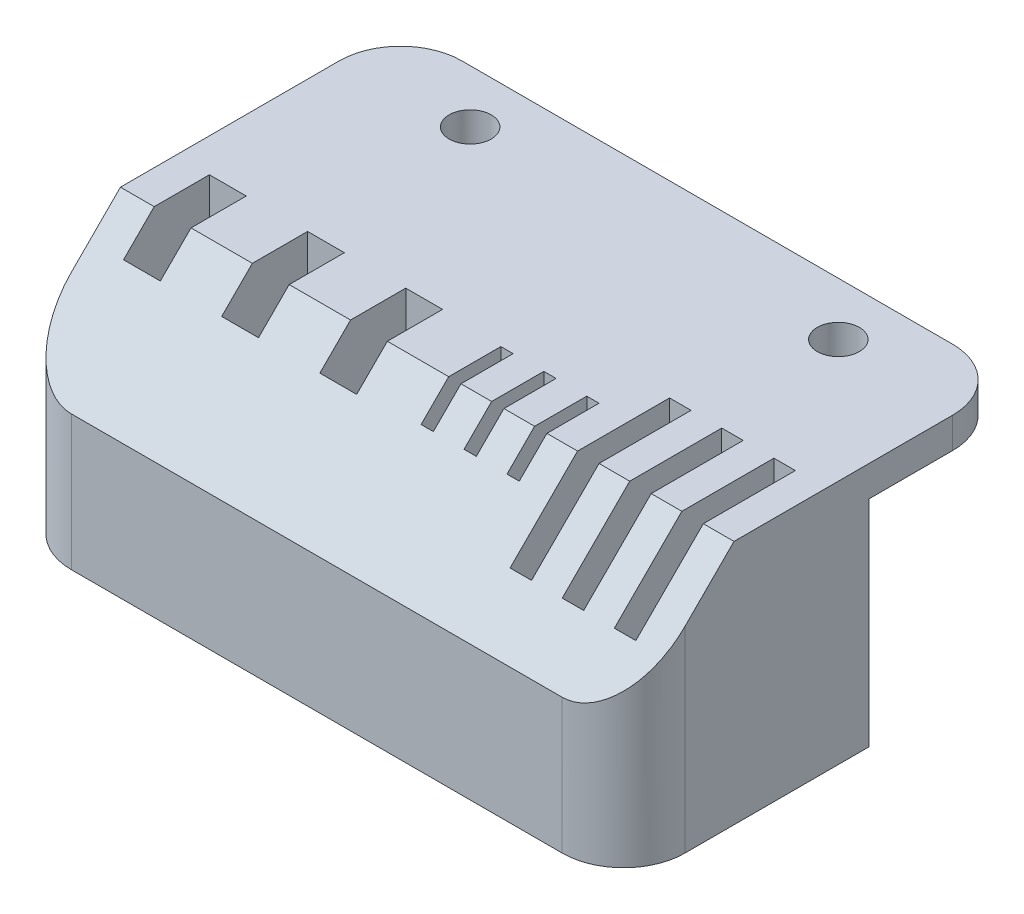
SolidWorks part; units mm, degrees
ref_plane "Front" through (0, 0, 0) normal (0, 0, 1) x (1, 0, 0)
ref_plane "Top" through (0, 0, 0) normal (0, 1, 0) x (1, 0, 0)
ref_plane "Right" through (0, 0, 0) normal (1, 0, 0) x (0, 0, -1)
sketch "Sketch1" plane through (0, 0, 0) normal (0, 1, 0) x (1, 0, 0)
  line L1 (-50, -15) -> (50, -15)
  line L2 (-50, -15) -> (-50, 15)
  line L3 (-50, 15) -> (50, 15)
  line L4 (50, -15) -> (50, 15)
  line L5 (-50, -15) -> (50, 15) construction
  line L6 (-50, 15) -> (50, -15) construction
  point P0 (0, 0)
  dimension "D1" = 30
  dimension "D2" = 100
extrude "Boss-Extrude1" add sketch "Sketch1" along normal blind 5
sketch "Sketch2" plane through (0, 0, 15) normal (0, 0, 1) x (1, 0, 0)
  line L1 (-50, 5) -> (50, 5)
  line L2 (-50, 5) -> (-50, -35)
  line L3 (-50, -35) -> (50, -35)
  line L4 (50, 5) -> (50, -35)
  dimension "D1" = 40
extrude "Boss-Extrude2" add sketch "Sketch2" along normal blind 40
sketch "Sketch3" plane through (0, 5, 0) normal (0, 1, 0) x (1, 0, 0)
  line L0 (50, -35) -> (-50, -35) construction
  line L1 (50, -55) -> (50, 15) construction
  line L2 (-50, 15) -> (-50, -55) construction
  line L3 (50, -55) -> (50, -15) construction
  line L4 (50, -55) -> (50, -15)
  line L6 (45, -48) -> (41.5, -48)
  line L7 (45, -48) -> (45, -22)
  line L8 (45, -22) -> (41.5, -22)
  line L9 (41.5, -48) -> (41.5, -22)
  line L10 (45, -48) -> (41.5, -22) construction
  line L11 (45, -22) -> (41.5, -48) construction
  line L12 (36.5, -48) -> (33, -48)
  line L13 (36.5, -48) -> (36.5, -22)
  line L14 (36.5, -22) -> (33, -22)
  line L15 (33, -48) -> (33, -22)
  line L16 (36.5, -48) -> (33, -22) construction
  line L17 (36.5, -22) -> (33, -48) construction
  line L18 (28, -48) -> (24.5, -48)
  line L19 (28, -48) -> (28, -22)
  line L20 (28, -22) -> (24.5, -22)
  line L21 (24.5, -48) -> (24.5, -22)
  line L22 (28, -48) -> (24.5, -22) construction
  line L23 (28, -22) -> (24.5, -48) construction
  point P8 (34.75, -35)
  point P9 (43.25, -35)
  point P18 (26.25, -35)
  dimension "D1" = 5
  dimension "D2" = 3.5
  dimension "D3" = 26
  dimension "D4" = 5
  dimension "D5" = 5
extrude "Cut-Extrude1" cut sketch "Sketch3" against normal blind 25 contours L9 L6 L7 L8 | L15 L12 L13 L14 | L21 L18 L19 L20 region at (43.25, 5, 35) region at (34.75, 5, 35) region at (26.25, 5, 35)
sketch "Sketch4" plane through (0, 5, 0) normal (0, 1, 0) x (1, 0, 0)
  line L0 (24.5, -35) -> (-49975.5, -35) construction
  line L1 (24.5, -48) -> (24.5, -22) construction
  line L3 (19.5, -41.5) -> (17.5, -41.5)
  line L4 (19.5, -41.5) -> (19.5, -28.5)
  line L5 (19.5, -28.5) -> (17.5, -28.5)
  line L6 (17.5, -41.5) -> (17.5, -28.5)
  line L7 (19.5, -41.5) -> (17.5, -28.5) construction
  line L8 (19.5, -28.5) -> (17.5, -41.5) construction
  line L9 (12.5, -41.5) -> (10.5, -41.5)
  line L10 (12.5, -41.5) -> (12.5, -28.5)
  line L11 (12.5, -28.5) -> (10.5, -28.5)
  line L12 (10.5, -41.5) -> (10.5, -28.5)
  line L13 (12.5, -41.5) -> (10.5, -28.5) construction
  line L14 (12.5, -28.5) -> (10.5, -41.5) construction
  line L15 (5.5, -41.5) -> (3.5, -41.5)
  line L16 (5.5, -41.5) -> (5.5, -28.5)
  line L17 (5.5, -28.5) -> (3.5, -28.5)
  line L18 (3.5, -41.5) -> (3.5, -28.5)
  line L19 (5.5, -41.5) -> (3.5, -28.5) construction
  line L20 (5.5, -28.5) -> (3.5, -41.5) construction
  point P4 (24.5, -35)
  point P5 (18.5, -35)
  point P10 (11.5, -35)
  point P15 (4.5, -35)
  dimension "D1" = 5
  dimension "D2" = 2
  dimension "D3" = 5
  dimension "D4" = 5
  dimension "D5" = 13
extrude "Cut-Extrude2" cut sketch "Sketch4" against normal blind 10
sketch "Sketch5" plane through (0, 5, 0) normal (0, 1, 0) x (1, 0, 0)
  line L0 (3.5, -35) -> (-49996.5, -35) construction
  line L1 (3.5, -28.5) -> (3.5, -41.5) construction
  line L3 (-6.5, -42) -> (-12.5, -42)
  line L4 (-6.5, -42) -> (-6.5, -28)
  line L5 (-6.5, -28) -> (-12.5, -28)
  line L6 (-12.5, -42) -> (-12.5, -28)
  line L7 (-6.5, -42) -> (-12.5, -28) construction
  line L8 (-6.5, -28) -> (-12.5, -42) construction
  line L9 (-22.5, -42) -> (-28.5, -42)
  line L10 (-22.5, -42) -> (-22.5, -28)
  line L11 (-22.5, -28) -> (-28.5, -28)
  line L12 (-28.5, -42) -> (-28.5, -28)
  line L13 (-22.5, -42) -> (-28.5, -28) construction
  line L14 (-22.5, -28) -> (-28.5, -42) construction
  line L15 (-38.5, -42) -> (-44.5, -42)
  line L16 (-38.5, -42) -> (-38.5, -28)
  line L17 (-38.5, -28) -> (-44.5, -28)
  line L18 (-44.5, -42) -> (-44.5, -28)
  line L19 (-38.5, -42) -> (-44.5, -28) construction
  line L20 (-38.5, -28) -> (-44.5, -42) construction
  point P4 (3.5, -35)
  point P5 (-9.5, -35)
  point P10 (-25.5, -35)
  point P15 (-41.5, -35)
  dimension "D1" = 6
  dimension "D2" = 14
  dimension "D3" = 10
  dimension "D4" = 10
  dimension "D5" = 10
extrude "Cut-Extrude3" cut sketch "Sketch5" against normal through all
chamfer "Chamfer1" distance 18 angle 45 1 edges at (0, 5, 55)
sketch "Sketch6" plane through (0, 5, 0) normal (0, 1, 0) x (1, 0, 0)
  line L0 (30, 0) -> (-30, 0) construction
  circle A0 centre (-30, 0) radius 3.429
  circle A1 centre (30, 0) radius 3.429
  point P4 (0, 0)
  dimension "D1" = 6.858
  dimension "D2" = 60
extrude "Cut-Extrude4" cut sketch "Sketch6" against normal through all
sketch "Sketch7" plane through (0, 5, 0) normal (0, 1, 0) x (1, 0, 0)
  line L0 (50, -37) -> (50, 15) construction
  line L1 (-50, 15) -> (50, 15)
  line L2 (-50, 15) -> (-50, 8.65)
  line L3 (-50, 8.65) -> (50, 8.65)
  line L4 (50, 15) -> (50, 8.65)
  point P5 (50, 8.6737)
  dimension "D1" = 6.35
extrude "Cut-Extrude5" cut sketch "Sketch7" against normal through all
fillet "Fillet1" radius 10 4 edges at (-50, -24, 55) (50, -24, 55) (-50, 2.5, -8.65) (50, 2.5, -8.65)
